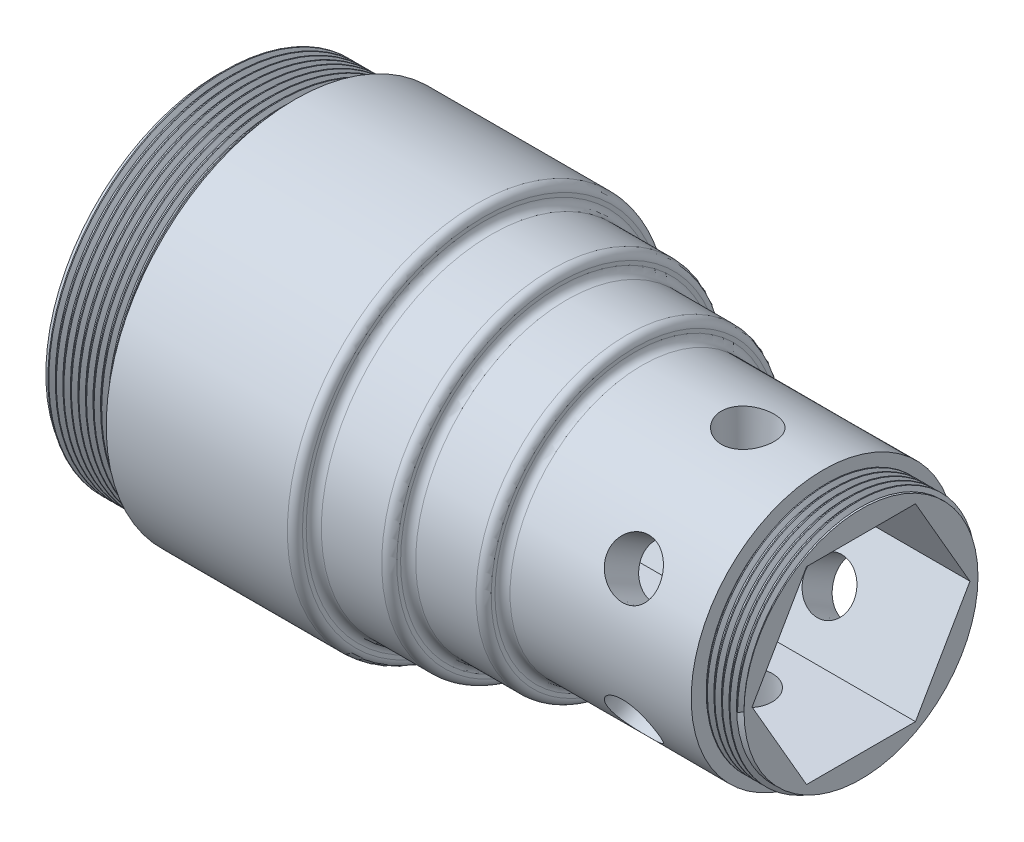
SolidWorks part; units mm, degrees
ref_plane "Front Plane" through (0, 0, 0) normal (0, 0, 1) x (1, 0, 0)
ref_plane "Top Plane" through (0, 0, 0) normal (0, 1, 0) x (1, 0, 0)
ref_plane "Right Plane" through (0, 0, 0) normal (1, 0, 0) x (0, 0, -1)
sketch "Sketch1" plane through (0, 0, 0) normal (0, 0, 1) x (1, 0, 0)
  line L1 (25, 18.5) -> (49, 18.5)
  line L2 (50, 17.5) -> (50, 2.5)
  line L3 (45, 15.5) -> (15, 15.5)
  line L7 (3, -6.5) -> (-21.0203, -6.5) construction
  line L8 (25, 18.5) -> (25, 16.5)
  line L9 (50, 2.5) -> (45, 2.5)
  line L10 (45, 2.5) -> (45, 15.5)
  line L11 (25, 16.5) -> (15, 16.5)
  line L12 (15, 16.5) -> (15, 15.5)
  line L14 (15, 15.5) -> (15, -6.5)
  arc A3 (50, 17.5) -> (49, 18.5) centre (49, 17.5) ccw
  point P12 (50, 18.5)
  dimension "D4" = 15
  dimension "D7" = 1
  dimension "D2" = 9
  dimension "D3" = 22
  dimension "D5" = 45
  dimension "D6" = 2.5
  dimension "10" = 5
  dimension "D8" = 3
  dimension "D10" = 2
  dimension "D11" = 10
revolve "Revolve1" add sketch "Sketch1" angle 360 about L7 region at (37, 18.1152, 0)
sketch "Sketch16" plane through (50, 0, 0) normal (1, 0, 0) x (0, 0, -1)
  line L1 (14.4338, -6.5) -> (7.2169, 6)
  line L2 (7.2169, 6) -> (-7.2169, 6)
  line L3 (-7.2169, 6) -> (-14.4338, -6.5)
  line L4 (-14.4338, -6.5) -> (-7.2169, -19)
  line L5 (-7.2169, -19) -> (7.2169, -19)
  line L6 (7.2169, -19) -> (14.4338, -6.5)
  circle A0 centre (0, -6.5) radius 12.5 construction
  circle A1 centre (0, -6.5) radius 20
  circle A2 centre (0, -6.5) radius 17.5
  circle A3 centre (0, -6.5) radius 22.5
  circle A4 centre (0, -6.5) radius 25 construction
  circle A5 centre (0, -6.5) radius 15.5
  circle M9 centre (0, -6.5) radius 9
  dimension "D1" = 25
  dimension "D3" = 40
  dimension "D4" = 35
  dimension "D5" = 45
  dimension "D6" = 31
  dimension "D2" = 12.5
extrude "Boss-Extrude2" add sketch "Sketch16" along normal blind 45 contours A2 M9 region at (50, -6.5, 17.005)
extrude "Boss-Extrude5" add sketch "Sketch16<6>" along normal blind 50 contours A5 L6 L5 L4 L3 L2 L1 region at (50, -6.5, 15.0616)
sketch "Sketch16<6>" plane through (50, 0, 0) normal (1, 0, 0) x (0, 0, -1) same geometry as "Sketch16"
extrude "Boss-Extrude3" add sketch "Sketch16<4>" along normal blind 20 contours A1 A2 region at (50, -6.5, 19.4343)
sketch "Sketch16<4>" plane through (50, 0, 0) normal (1, 0, 0) x (0, 0, -1) same geometry as "Sketch16"
extrude "Boss-Extrude4" add sketch "Sketch16<5>" along normal blind 10 contours A3 A1 region at (50, -6.5, 21.8636)
sketch "Sketch16<5>" plane through (50, 0, 0) normal (1, 0, 0) x (0, 0, -1) same geometry as "Sketch16"
ref_plane "Plane2" through (85, 0, 0) normal (1, 0, 0) x (0, 0, -1)
sketch "Sketch18" plane through (85, 0, 0) normal (1, 0, 0) x (0, 0, -1)
  line L5 (0, 6) -> (0, 11)
  line L6 (7.2169, 6) -> (-7.2169, 6) construction
  line L7 (0, 11) -> (-3.5, 11)
  line L8 (-3.5, 11) -> (-3.25, 6)
  line L9 (-3.25, 6) -> (0, 6)
  circle A1 centre (0, -6.5) radius 17.5 construction
  dimension "D1" = 3.5
  dimension "D2" = 3.25
revolve "Cut-Revolve1" cut sketch "Sketch18" angle 360 about L5
pattern_circular "CirPattern2" count 6 over 360 about axis through (95, -6.5, 0) along (1, 0, 0) of "Cut-Revolve1"
thread "Thread2" pitch 1 method extrude profile "Thread Profile2" start angle 0, offset 0, length 5, pitch 1, diameter 31
ref_plane "Plane3" through (100, -6.5, 15.5) normal (0, -1, 0) x (0, 0, 1)
sketch "Thread Profile2" plane through (100, -6.5, 15.5) normal (0, -1, 0) x (0, 0, 1)
  line L0 (0, 0) -> (0, 1) construction
  line L1 (0, 0) -> (0.5413, 0.3125)
  line L2 (0.5413, 0.3125) -> (0.5413, 0.4375)
  line L3 (0.5413, 0.4375) -> (0, 0.75)
  line L4 (0.5413, 0.375) -> (0, 0.375) construction
  line L11 (0, 0) -> (0, 0.75)
  point P2 (0, 0)
  dimension "Pitch" = 1
  dimension "Profile_Angle" = 60
  dimension "Profile_Land" = 0.125
  dimension "Profile_Height" = 0.5413
fillet "Fillet1" radius 1 1 edges at (60, 16, 0) type face fillet first side face at (60, 16, 0) second side face at (60, 13.5, 0)
fillet "Fillet2" radius 1 1 edges at (70, 13.5, 0) type face fillet first side face at (60, 13.5, 0) second side face at (70, 11, 0)
fillet "Fillet3" radius 1 1 edges at (50, -29, 0) type face fillet first side face at (50, -29, 0) second side face at (59, 16, 0)
fillet "Fillet4" radius 1 1 edges at (60, 13.5, 0) type face fillet first side face at (60, 15, 0) second side face at (69, 13.5, 0)
fillet "Fillet5" radius 1 1 edges at (70, 11, 0) type face fillet first side face at (70, 12.5, 0) second side face at (88.0515, -13.7312, -15.9361)
thread "Thread4" pitch 1 method extrude profile "Thread Profile4" start angle 0, offset 0, length 10, pitch 1, diameter 46
ref_plane "Plane5" through (15, -6.5, -23) normal (0, -1, 0) x (0, 0, -1)
sketch "Thread Profile4" plane through (15, -6.5, -23) normal (0, -1, 0) x (0, 0, -1)
  line L0 (0, 0) -> (0, 1) construction
  line L1 (0, 0) -> (0.5413, 0.3125)
  line L2 (0.5413, 0.3125) -> (0.5413, 0.4375)
  line L3 (0.5413, 0.4375) -> (0, 0.75)
  line L4 (0.5413, 0.375) -> (0, 0.375) construction
  line L11 (0, 0) -> (0, 0.75)
  point P2 (0, 0)
  dimension "Pitch" = 1
  dimension "Profile_Angle" = 60
  dimension "Profile_Land" = 0.125
  dimension "Profile_Height" = 0.5413
sketch "Sketch19" plane through (50, 0, 0) normal (1, 0, 0) x (0, 0, -1)
  circle A0 centre (0, -6.5) radius 11
  dimension "D1" = 22
extrude "Cut-Extrude1" cut sketch "Sketch19" against normal blind 1.6
sketch "Sketch24" plane through (48.4, 0, 0) normal (1, 0, 0) x (0, 0, -1)
  circle A0 centre (0, -6.5) radius 9 construction
  circle A1 centre (0, -6.5) radius 11 construction
  point P0 (0, 3.5)
  point P3 (0, 0)
  dimension "D1" = 10
  dimension "D2" = 10
hole_wizard "Tap Drill for M1.2x0.25 Tap1" positions "Sketch24" profile "Sketch23" hole size "M1.2x0.25" standard "ANSI Metric"
sketch "Sketch23" plane through (48.4, 3.5, 0) normal (0, 1, 0) x (0, 0, -1)
  line L0 (0, 0) -> (0, 2.2854)
  line L1 (0, 2.2854) -> (0.475, 2)
  line L2 (0.475, 2) -> (0.475, 0.025)
  line L3 (0.475, 0.025) -> (0.5, 0)
  line L5 (0.5, 0) -> (0, 0)
  line L6 (-0.475, 0.025) -> (-0.5, 0) construction
  line L10 (0, 2.2854) -> (-0.475, 2) construction
  line L11 (0, -6.35) -> (0, 107.95) construction
  dimension "Hole Dia." = 0.95
  dimension "Hole Depth" = 2
  dimension "Near C'Sink Dia." = 1
  dimension "Near C'Sink Angle" = 90
  dimension "Drill Angle" = 118
pattern_circular "CirPattern3" count 4 over 360 about axis through (48.4, -6.5, 0) along (-1, 0, 0) of "Tap Drill for M1.2x0.25 Tap1"
